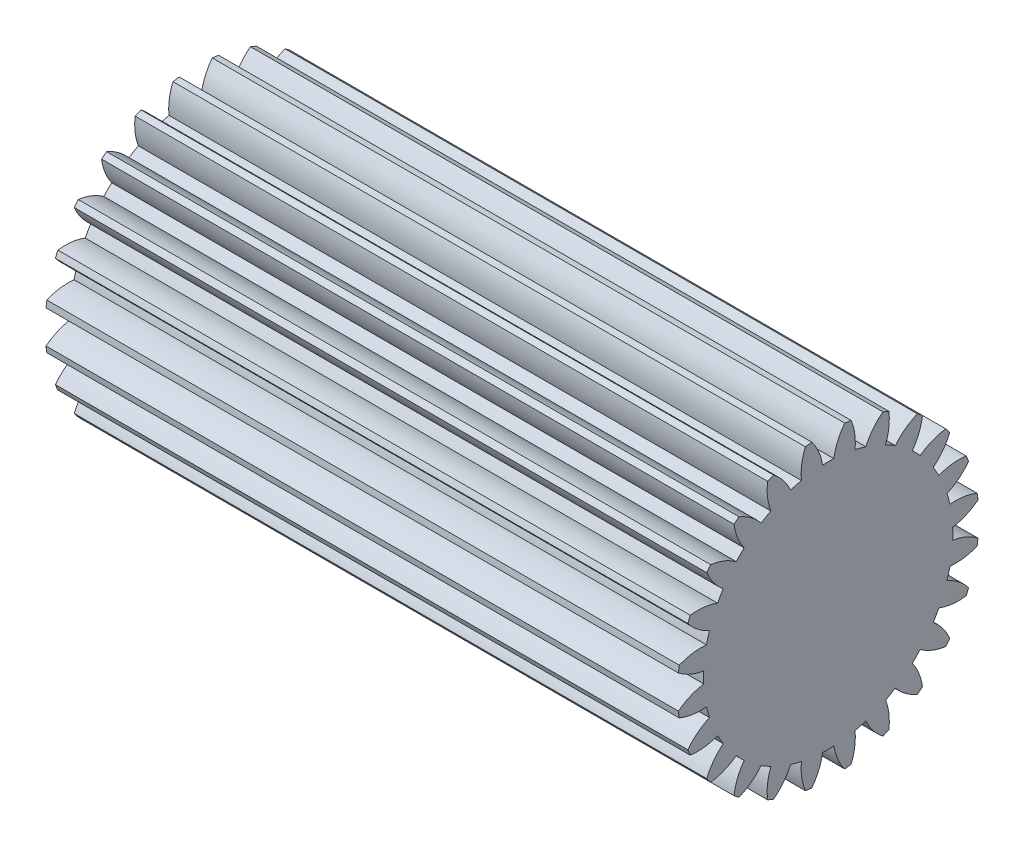
SolidWorks part; units mm, degrees
ref_plane "Plane1" through (0, 0, 0) normal (0, 0, 1) x (1, 0, 0)
ref_plane "Plane2" through (0, 0, 0) normal (0, 1, 0) x (1, 0, 0)
ref_plane "Plane3" through (0, 0, 0) normal (1, 0, 0) x (0, 0, -1)
sketch "HoldingSke" plane through (0, 0, 0) normal (0, 1, 0) x (1, 0, 0)
  line L0 (0, 0) -> (0.9135, -0.4067)
  line L1 (-15, 0) -> (100, 0) construction
  line L2 (0, 0) -> (-2.1039, 2.3779)
  line L3 (0, 0) -> (-11.863, 4.5341)
  line L4 (0, 0) -> (7.8894, 3.5126)
  line L5 (0, 0) -> (-46.8476, -17.4728)
  line L6 (0, 0) -> (-9.9476, -6.7116)
  line L7 (-2.1039, 2.3779) -> (8.6586, 51.2059)
  line L8 (-76.2, 54.61) -> (-76.1, 54.61)
  line L9 (-71.009, 38.7566) -> (-53.1078, 45.2721)
  line L10 (-76.2, 71.12) -> (104.1128, 71.12)
  line L11 (0, 0) -> (-12, 0)
  line L12 (-76.2, 101.6) -> (-76.162, 101.6)
  line L13 (24.9733, 27.94) -> (52.9518, 28.4284)
  line L14 (24.9733, 27.94) -> (24.9743, 27.94)
  line L15 (24.9733, 27.94) -> (100.4006, 29.5858)
  line L16 (-63.627, -1) -> (-12.827, -1)
  circle A0 centre (0, 0) radius 0.4
  circle A1 centre (0, 0) radius 10.749
  circle A2 centre (0, 0) radius 37.5
  circle A3 centre (0, 0) radius 0.4
  dimension "Num_teeth" = 24
  dimension "Pitch_radius" = 180.3128
  dimension "Width" = 12
sketch "BasProSke" plane through (0, 0, 0) normal (0, 1, 0) x (1, 0, 0)
  line L0 (-10, 0) -> (60, 0) construction
  line L1 (0, 0) -> (0, 13)
  line L2 (0, 0) -> (54.565, 0)
  line L3 (54.565, 0) -> (54.565, 13)
  line L4 (54.565, 13) -> (0, 13)
  dimension "Thickness" = 54.565
  dimension "Diameter" = 26
revolve "Base-Revolve" add sketch "BasProSke" angle 360 about L0
sketch "TooCutSke" plane through (0, 0, 0) normal (1, 0, 0) x (0, 0, -1)
  line L1 (0, 0) -> (0, 107) construction
  line L2 (0, 0) -> (-0.8513, 11.9698) construction
  line L3 (0, 0) -> (-3.127, 23.752) construction
  line L4 (-0.8513, 11.9698) -> (-1.5635, 11.876) construction
  arc A0 (0.4834, 10.7381) -> (-0.4834, 10.7381) centre (0, 0) ccw
  arc A1 (1.4409, 12.9455) -> (-1.4409, 12.9455) centre (0, 0) ccw
  circle A2 centre (0, 0) radius 12 construction
  circle A3 centre (0, 0) radius 11.2763 construction
  arc A4 (-0.4834, 10.7381) -> (-1.4409, 12.9455) centre (-5.2252, 9.9926) ccw
  arc A5 (1.4409, 12.9455) -> (0.4834, 10.7381) centre (5.2252, 9.9926) ccw
extrude "ToothCut" cut sketch "TooCutSke" along normal through all
fillet "Breaks" [suppressed] radius 0.02 tangent propagation no
fillet "RootFillets" [suppressed] radius 0.251
pattern_circular "TeethCuts" count 24 every 15 about axis through (-10, 0, 0) along (1, 0, 0) of "ToothCut", "RootFillets", "Breaks"
sketch "HubNeaOneSke" plane through (0, 0, 0) normal (-1, 0, 0) x (0, 0, 1)
  circle A0 centre (0, 0) radius 10.749
  dimension "Diameter" = 21.498
extrude "HubNearOne" [suppressed] add sketch "HubNeaOneSke" along normal blind 15.1851
sketch "HubNeaBotSke" plane through (0, 0, 0) normal (-1, 0, 0) x (0, 0, 1)
  circle A0 centre (0, 0) radius 10.749
  dimension "Diameter" = 21.498
extrude "HubNearBoth" [suppressed] add sketch "HubNeaBotSke" along normal blind 7.5925
ref_plane "FarPln" through (54.565, 0, 0) normal (1, 0, 0) x (0, 0, -1)
sketch "HubFarSke" plane through (54.565, 0, 0) normal (1, 0, 0) x (0, 0, -1)
  circle A0 centre (0, 0) radius 10.749
  dimension "Diameter" = 21.498
extrude "HubFar" [suppressed] add sketch "HubFarSke" along normal blind 7.5925
sketch "BorSke" plane through (0, 0, 0) normal (1, 0, 0) x (0, 0, -1)
  circle A0 centre (0, 0) radius 0.4
  dimension "Diameter" = 0.8
extrude "Bore" cut sketch "BorSke" along normal mid plane 100.0001
sketch "KeySke" plane through (0, 0, 0) normal (1, 0, 0) x (0, 0, -1)
  line L0 (-0.05, 0) -> (-0.05, 0.5)
  line L1 (-0.05, 0.5) -> (0.05, 0.5)
  line L2 (0.05, 0.5) -> (0.05, 0)
  line L3 (0, 0) -> (0, 34) construction
  line L4 (-0.05, 0) -> (0.05, 0)
  dimension "Width" = 0.1
extrude "Keyway" [suppressed] cut sketch "KeySke" along normal mid plane 100.0001
pattern_circular "Keyway2" [suppressed] count 2 every 90 about axis through (-10, 0, 0) along (1, 0, 0) reverse direction yes
scale "Scale1" scale about centroid uniform scaling yes scale factor 2
sketch "Sketch1" plane through (81.8451, 0, 0) normal (1, 0, 0) x (0, 0, -1)
  circle A0 centre (0, 0) radius 23.749 construction
  dimension "D1" = 47.498
equation "' \"Module@HoldingSke\" = 6.35"
equation "' \"Num_teeth@HoldingSke\" = 12"
equation "' \"Ap@HoldingSke\" =  20"
equation "' \"Ap@HoldingSke\" = 20"
equation "' \"Width@HoldingSke\" = 0.5 * 25.4"
equation "' \"Hub_dia@HoldingSke\"= 1 * 25.4"
equation "' \"Hub_dia@HoldingSke\" = 1 * 25.4"
equation "' \"Overall_len@HoldingSke\" = 1.0 * 25.4"
equation "' \"Bore@HoldingSke\" = 0.75 * 25.4"
equation "' \"T_dim@HoldingSke\" = 0.1 * 25.4"
equation "' \"Width@KeySke\" = 0.25 * 25.4"
equation "' \"Show_teeth@HoldingSke\" = 13"
equation "' \"Backlash@HoldingSke\" = 0.009 * 25.4"
equation "' \"Addendum_fac@HoldingSke\" = 1.0"
equation "' \"Dedendum_fac@HoldingSke\" = 1.25"
equation "' \"Dedendum_add@HoldingSke\" = 0.00005 * 25.4"
equation "' \"Clearance_fac@HoldingSke\" = 0.25"
equation "\"Pitch@HoldingSke\" = 1 / \"Module@HoldingSke\""
equation "\"Overcut_dia@TooCutSke\" = (\"Num_teeth@HoldingSke\" + 2 * \"Addendum_fac@HoldingSke\") / \"Pitch@HoldingSke\" + 0.002 * 25.4"
equation "\"Pitch_dia@TooCutSke\" = \"Num_teeth@HoldingSke\" / \"Pitch@HoldingSke\""
equation "\"Base_dia@TooCutSke\" = \"Num_teeth@HoldingSke\" / \"Pitch@HoldingSke\" * cos((\"Ap@HoldingSke\"  * 3.14159265 / 180))"
equation "\"Root_dia@TooCutSke\" = (\"Num_teeth@HoldingSke\" + 2) / \"Pitch@HoldingSke\" - 2 * (\"Addendum_fac@HoldingSke\" + \"Dedendum_fac@HoldingSke\") / \"Pitch@HoldingSke\" - \"Dedendum_add@HoldingSke\" * 2"
equation "\"Half_ang@TooCutSke\" = 180 / \"Num_teeth@HoldingSke\""
equation "\"Half_CT@TooCutSke\" = \"Num_teeth@HoldingSke\" / \"Pitch@HoldingSke\" * sin((3.14159265 / 2 / \"Num_teeth@HoldingSke\")) / 2 - 7 * \"Backlash@HoldingSke\" / 4"
equation "\"Flank_rad@TooCutSke\" = \"Num_teeth@HoldingSke\" / \"Pitch@HoldingSke\" / 5"
equation "\"Radius@RootFillets\" = \"Clearance_fac@HoldingSke\" / \"Pitch@HoldingSke\" + \"Dedendum_add@HoldingSke\""
equation "\"Break_rad@Breaks\" = 0.02 / \"Pitch@HoldingSke\""
equation "\"Thickness@HoldingSke\" = \"Width@HoldingSke\""
equation "\"OAL@HoldingSke\" = \"Thickness@HoldingSke\""
equation "\"MHD@HoldingSke\" = (\"Num_teeth@HoldingSke\" + 2) / \"Pitch@HoldingSke\" - 2 * (\"Addendum_fac@HoldingSke\" + \"Dedendum_fac@HoldingSke\")  / \"Pitch@HoldingSke\" - \"Dedendum_add@HoldingSke\" * 2"
equation "\"MBD@HoldingSke\" = (\"Num_teeth@HoldingSke\" + 2) / \"Pitch@HoldingSke\" - 2 * (\"Addendum_fac@HoldingSke\" + \"Dedendum_fac@HoldingSke\")  / \"Pitch@HoldingSke\" - \"Dedendum_add@HoldingSke\" * 2 - 0.002 * 25.4"
equation "\"MHD@HoldingSke\" = ((sgn( \"MHD@HoldingSke\" - \"Hub_dia@HoldingSke\" )-1)*( \"MHD@HoldingSke\" - \"Hub_dia@HoldingSke\" ))/-2+ \"Hub_dia@HoldingSke\""
equation "\"MBD@HoldingSke\" = ((sgn( \"MBD@HoldingSke\" - \"Bore@HoldingSke\" )-1)*( \"MBD@HoldingSke\" - \"Bore@HoldingSke\" ))/-2+ \"Bore@HoldingSke\""
equation "\"OAL@HoldingSke\" = ((sgn( \"OAL@HoldingSke\" - \"Overall_len@HoldingSke\" )+1)*( \"OAL@HoldingSke\" - \"Overall_len@HoldingSke\" ))/2 + \"Overall_len@HoldingSke\" + 0.000002 * 25.4"
equation "\"Num_teeth@TeethCuts\" = int( \"Show_teeth@HoldingSke\" ) + 1"
equation "\"Num_teeth@TeethCuts\" = ((sgn( \"Num_teeth@TeethCuts\" - \"Num_teeth@HoldingSke\" )-1)*( \"Num_teeth@TeethCuts\" - \"Num_teeth@HoldingSke\" ))/-2+ \"Num_teeth@HoldingSke\""
equation "\"Num_teeth@TeethCuts\" = ((sgn( \"Num_teeth@TeethCuts\" - 2.0)+1)*( \"Num_teeth@TeethCuts\" - 2.0))/2 +2.0"
equation "\"Angle@TeethCuts\" = 360.0 / \"Num_teeth@HoldingSke\""
equation "\"Diameter@BasProSke\" = (\"Num_teeth@HoldingSke\" + 2 * \"Addendum_fac@HoldingSke\") / \"Pitch@HoldingSke\""
equation "' \"Fillet_rad@BasProSke\" =  \"Thickness@HoldingSke\" * 0.05"
equation "' \"Fillet_rad@BasProSke\" = \"Thickness@HoldingSke\" * 0.05"
equation "\"MHD@HoldingSke\" = ((sgn( \"MHD@HoldingSke\" - \"Root_dia@TooCutSke\" )-1)*( \"MHD@HoldingSke\" - \"Root_dia@TooCutSke\" ))/-2+ \"Root_dia@TooCutSke\""
equation "\"Diameter@HubNeaOneSke\" = \"MHD@HoldingSke\""
equation "\"Length@HubNearOne\" = \"OAL@HoldingSke\" - \"Thickness@BasProSke\""
equation "\"Diameter@HubNeaBotSke\" = \"MHD@HoldingSke\""
equation "\"Length@HubNearBoth\" = ( \"OAL@HoldingSke\" - \"Thickness@BasProSke\" ) / 2.0"
equation "\"Thickness@FarPln\" = \"Thickness@BasProSke\""
equation "\"Diameter@HubFarSke\" = \"MHD@HoldingSke\""
equation "\"Length@HubFar\" = ( \"OAL@HoldingSke\" - \"Thickness@BasProSke\" ) / 2.0"
equation "\"Diameter@BorSke\" = \"MBD@HoldingSke\""
equation "\"D1@Bore\" = \"OAL@HoldingSke\" * 2.0"
equation "\"D1@Keyway\" = \"OAL@HoldingSke\" * 2.0"
equation "\"Offset@KeySke\" = \"T_dim@HoldingSke\" + \"MBD@HoldingSke\" / 2.0"
